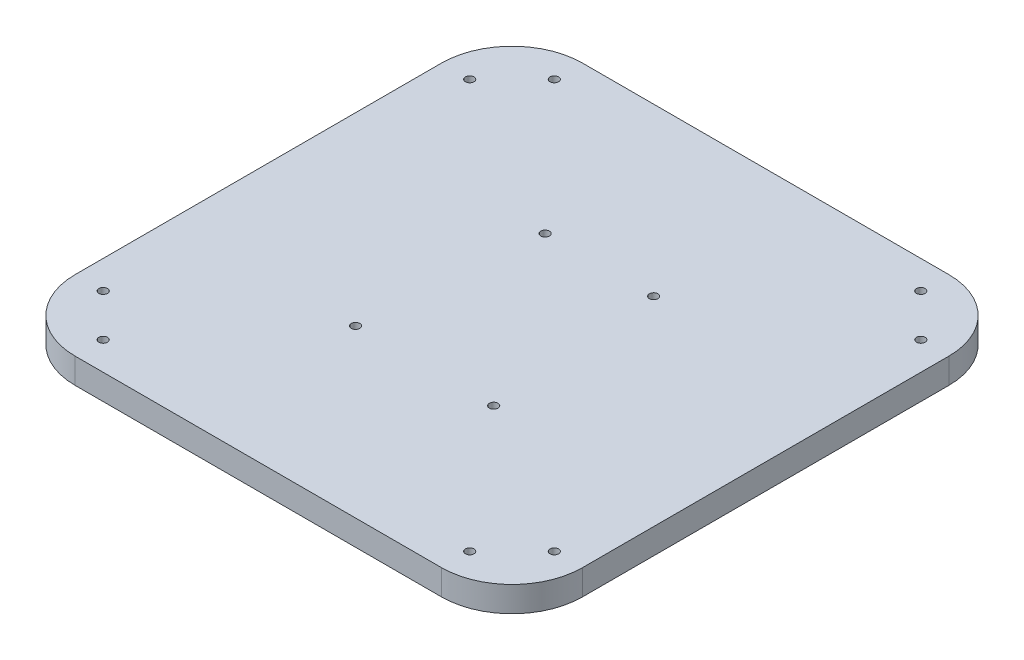
SolidWorks part; units mm, degrees
ref_plane "Front Plane" through (0, 0, 0) normal (0, 0, 1) x (1, 0, 0)
ref_plane "Top Plane" through (0, 0, 0) normal (0, 1, 0) x (1, 0, 0)
ref_plane "Right Plane" through (0, 0, 0) normal (1, 0, 0) x (0, 0, -1)
sketch "Sketch1" plane through (0, 0, 0) normal (0, 1, 0) x (1, 0, 0)
  line L1 (-65, -90) -> (65, -90)
  line L2 (-90, -65) -> (-90, 65)
  line L3 (-65, 90) -> (65, 90)
  line L4 (90, -65) -> (90, 65)
  arc A0 (-90, 65) -> (-65, 90) centre (-65, 65) cw
  arc A1 (65, 90) -> (90, 65) centre (65, 65) cw
  arc A2 (90, -65) -> (65, -90) centre (65, -65) cw
  arc A3 (-65, -90) -> (-90, -65) centre (-65, -65) cw
  point P4 (-90, 0)
  point P6 (0, 90)
  dimension "D3" = 25
  dimension "D1" = 180
  dimension "D2" = 180
extrude "Plate" add sketch "Sketch1" along normal blind 9
sketch "Sketch3" plane through (0, 9, 0) normal (0, 1, 0) x (1, 0, 0)
  line L0 (-65, 90) -> (-65, -90) construction
  line L1 (65, 90) -> (65, -90) construction
  line L2 (-90, 65) -> (90, 65) construction
  line L3 (-90, -65) -> (90, -65) construction
  circle A0 centre (-65, 80) radius 1.525
  circle A1 centre (-80, 65) radius 1.525
  circle A2 centre (80, 65) radius 1.525
  circle A3 centre (80, -65) radius 1.525
  circle A4 centre (65, 80) radius 1.525
  circle A5 centre (65, -80) radius 1.525
  circle A6 centre (-65, -80) radius 1.525
  circle A7 centre (-80, -65) radius 1.525
  dimension "D1" = 3.05
  dimension "D2" = 15
  dimension "D3" = 15
  dimension "D4" = 15
  dimension "D5" = 15
  dimension "D6" = 15
  dimension "D7" = 15
  dimension "D8" = 15
  dimension "D9" = 15
extrude "Hex Holes" cut sketch "Sketch3" against normal through all
sketch "Sketch4" plane through (0, 9, 0) normal (0, 1, 0) x (1, 0, 0)
  line L0 (-90, -65) -> (-90, 65) construction
  line L1 (-65, -90) -> (65, -90) construction
  circle A0 centre (-24.5, -31) radius 1.525
  circle A1 centre (24.5, -31) radius 1.525
  circle A2 centre (-19.25, 31) radius 1.525
  circle A3 centre (19.25, 31) radius 1.525
  point P8 (0, 0)
  point P9 (0, 0)
  point P10 (0, 0)
  dimension "D1" = 3.05
  dimension "D2" = 62
  dimension "D3" = 49
  dimension "D4" = 5.25
  dimension "D5" = 38.5
  dimension "D6" = 65.5
  dimension "D7" = 59
extrude "Arduino Holes" cut sketch "Sketch4" against normal through all
